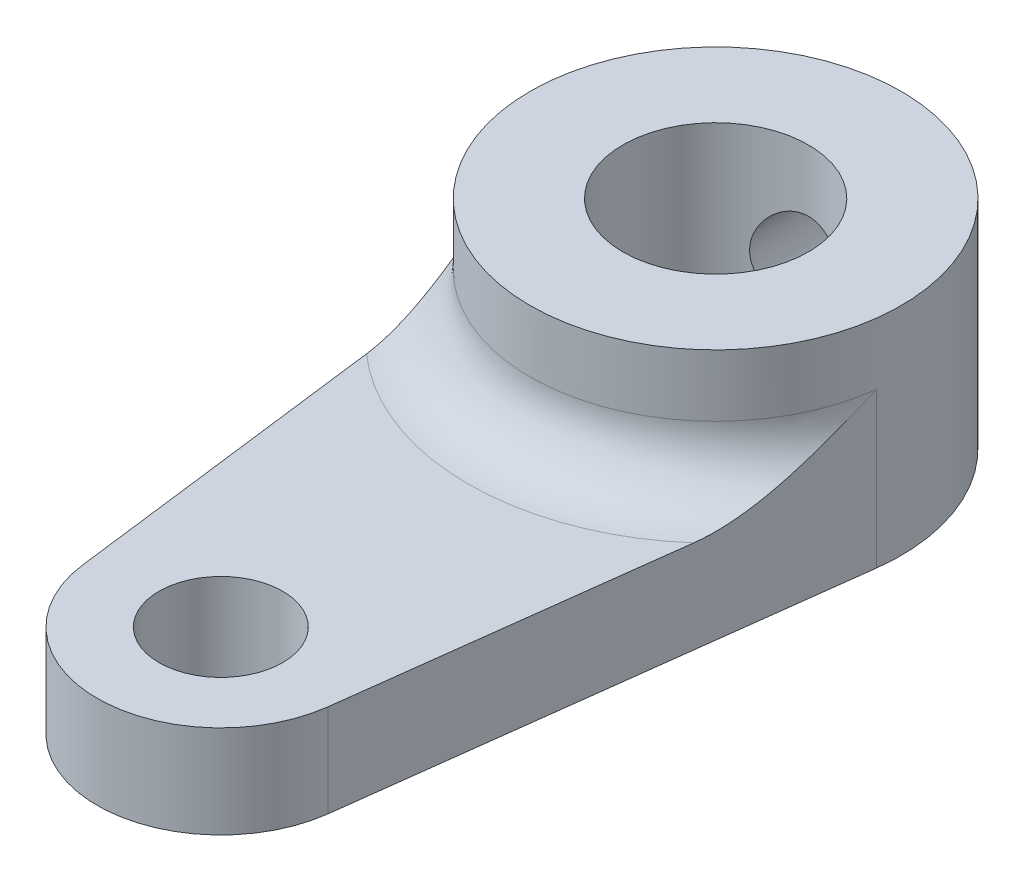
SolidWorks part; units mm, degrees
material "Alloy Steel (SS)"
ref_plane "Front Plane" through (0, 0, 0) normal (0, 0, 1) x (1, 0, 0)
ref_plane "Top Plane" through (0, 0, 0) normal (0, 1, 0) x (1, 0, 0)
ref_plane "Right Plane" through (0, 0, 0) normal (1, 0, 0) x (0, 0, -1)
sketch "Sketch1" plane through (0, 0, 0) normal (0, 1, 0) x (1, 0, 0)
  line L0 (-5.9529, -0.75) -> (-3.9686, -16.5)
  line L1 (5.9529, -0.75) -> (3.9686, -16.5)
  arc A0 (5.9529, -0.75) -> (-5.9529, -0.75) centre (0, 0) ccw
  arc A1 (-3.9686, -16.5) -> (3.9686, -16.5) centre (0, -16) ccw
  circle A2 centre (0, -16) radius 2
  dimension "D1" = 12
  dimension "D2" = 8
  dimension "D4" = 4
  dimension "D3" = 16
extrude "Boss-Extrude1" add sketch "Sketch1" along normal mid plane 3
sketch "Sketch2" plane through (0, 1.5, 0) normal (0, 1, 0) x (1, 0, 0)
  circle A0 centre (0, 0) radius 6
  dimension "D1" = 12
extrude "Boss-Extrude2" add sketch "Sketch2" along normal blind 4
sketch "Sketch3" plane through (0, 5.5, 0) normal (0, 1, 0) x (1, 0, 0)
  circle A0 centre (0, 0) radius 3
  dimension "D1" = 6
extrude "Cut-Extrude1" cut sketch "Sketch3" against normal through all
fillet "Fillet1" radius 2 1 edges at (0, 1.5, 6)
ref_plane "Plane1" through (0, 0, -6) normal (0, 0, 1) x (1, 0, 0)
sketch "Sketch4" plane through (0, 0, -6) normal (0, 0, 1) x (1, 0, 0)
  line L0 (-3.9686, -1.5) -> (3.9686, -1.5) construction
  circle A0 centre (0, 2) radius 1.5
  dimension "D1" = 3
  dimension "D2" = 3.5
extrude "Cut-Extrude2" cut sketch "Sketch4" along normal blind 4
cosmetic thread "Cosmetic Thread1" parameters "D2"=4
